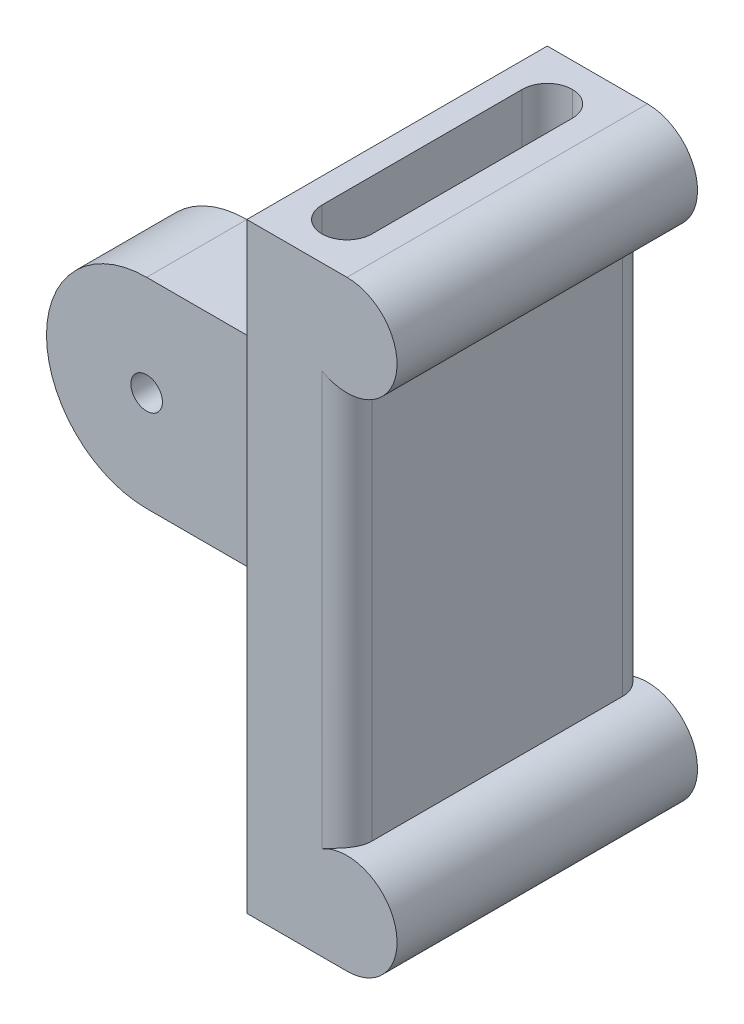
SolidWorks part; units mm, degrees
ref_plane "Front Plane" through (0, 0, 0) normal (0, 0, 1) x (1, 0, 0)
ref_plane "Top Plane" through (0, 0, 0) normal (0, 1, 0) x (1, 0, 0)
ref_plane "Right Plane" through (0, 0, 0) normal (1, 0, 0) x (0, 0, -1)
sketch "Sketch1" plane through (0, 0, 0) normal (0, 0, 1) x (1, 0, 0)
  line L1 (0, -12.7) -> (25.4, -12.7)
  line L3 (0, 12.7) -> (25.4, 12.7)
  line L4 (25.4, -12.7) -> (25.4, 12.7)
  circle A0 centre (0, 0) radius 2
  circle A1 centre (0, 0) radius 12.7
  dimension "D1" = 25.4
  dimension "D2" = 4
  dimension "D3" = 25.4
extrude "Boss-Extrude1" add sketch "Sketch1" along normal blind 12.7 contours A1 A0 | A1 L1 L4 L3 region at (17.4268, 0, 0) region at (-12.3408, 0, 0)
sketch "Sketch2" plane through (25.4, 0, 0) normal (1, 0, 0) x (0, 0, -1)
  line L1 (-25.4, 38.1) -> (12.7, 38.1)
  line L2 (-25.4, 38.1) -> (-25.4, -38.1)
  line L3 (-25.4, -38.1) -> (12.7, -38.1)
  line L4 (12.7, 38.1) -> (12.7, -38.1)
  line L5 (-12.7, 12.7) -> (0, 12.7) construction
  line L6 (-12.7, -12.7) -> (-12.7, 12.7) construction
  line L7 (0, -12.7) -> (0, 12.7) construction
  line L8 (-12.7, -12.7) -> (0, -12.7) construction
  dimension "D1" = 25.4
  dimension "D2" = 25.4
  dimension "D3" = 12.7
  dimension "D4" = 12.7
extrude "Boss-Extrude2" add sketch "Sketch2" along normal blind 12.7 contours L1 L4 L3 L2
fillet "Fillet1" radius 12.7 4 edges at (25.4, -12.7, 6.35) (25.4, 0, 12.7) (25.4, 12.7, 6.35) (25.4, 0, 0)
sketch "Sketch3" plane through (0, 38.1, 0) normal (0, 1, 0) x (1, 0, 0)
  line L1 (28.575, 9.525) -> (34.925, 9.525)
  line L2 (28.575, 9.525) -> (28.575, -22.225)
  line L3 (28.575, -22.225) -> (34.925, -22.225)
  line L4 (34.925, 9.525) -> (34.925, -22.225)
  line L5 (38.1, -25.4) -> (38.1, 12.7) construction
  line L6 (38.1, 12.7) -> (25.4, 12.7) construction
  line L7 (38.1, -25.4) -> (25.4, -25.4) construction
  line L9 (25.4, 12.7) -> (25.4, -25.4) construction
  point P12 (31.75, -25.4)
  dimension "D1" = 3.175
  dimension "D2" = 3.175
  dimension "D3" = 3.175
  dimension "D4" = 3.175
extrude "Cut-Extrude1" cut sketch "Sketch3" against normal through all
sketch "Sketch4" plane through (0, 0, 25.4) normal (0, 0, 1) x (1, 0, 0)
  line L0 (38.1, 38.1) -> (38.1, -38.1) construction
  line L1 (38.1, 38.1) -> (25.4, 38.1) construction
  line L2 (38.1, 38.1) -> (38.1, 25.4)
  line L3 (38.1, -25.4) -> (38.1, -38.1)
  arc A0 (38.1, 38.1) -> (38.1, 25.4) centre (38.1, 31.75) cw
  arc A1 (38.1, -38.1) -> (38.1, -25.4) centre (38.1, -31.75) ccw
  dimension "D1" = 12.7
  dimension "D2" = 12.7
extrude "Boss-Extrude3" add sketch "Sketch4" against normal up to vertex (38.1 mm away) up to point (38.1, 38.1, -12.7)
fillet "Fillet2" radius 3.175 6 edges at (34.925, 0, 22.225) (28.575, 0, 22.225) (34.925, 0, -9.525) (28.575, 0, -9.525) (38.1, 0, 25.4) (38.1, 0, -12.7)
